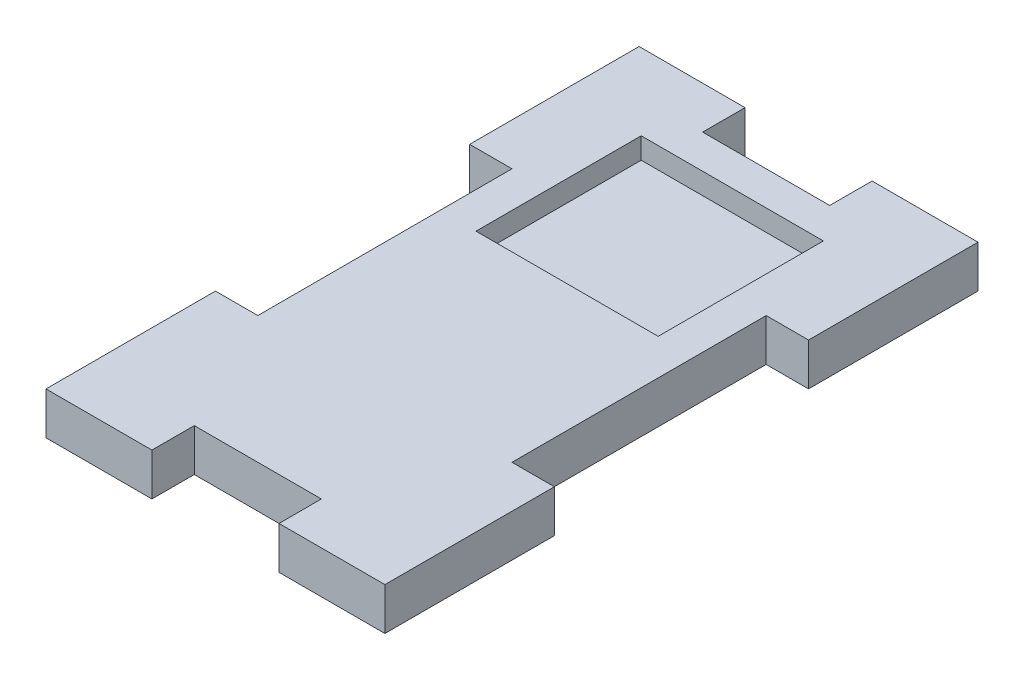
SolidWorks part; units mm, degrees
material "Acrylic (Medium-high impact)"
ref_plane "Front Plane" through (0, 0, 0) normal (0, 0, 1) x (1, 0, 0)
ref_plane "Top Plane" through (0, 0, 0) normal (0, 1, 0) x (1, 0, 0)
ref_plane "Right Plane" through (0, 0, 0) normal (1, 0, 0) x (0, 0, -1)
sketch "Sketch1" plane through (0, 0, 0) normal (0, 1, 0) x (1, 0, 0)
  line L1 (0, 0) -> (40, 0)
  line L2 (0, 0) -> (0, 70)
  line L3 (0, 70) -> (40, 70)
  line L4 (40, 0) -> (40, 70)
  dimension "D1" = 70
  dimension "D2" = 40
extrude "Boss-Extrude1" add sketch "Sketch1" along normal blind 5
sketch "Sketch3" plane through (0, 5, 0) normal (0, 1, 0) x (1, 0, 0)
  point P0 (15.5429, 20.9788)
  point P1 (15.5429, 20.9788)
sketch "Sketch4" plane through (0, 0, 0) normal (0, -1, 0) x (1, 0, 0)
  line L0 (20, 0) -> (20, -70) construction
  line L1 (30.75, -61) -> (9.25, -61)
  line L2 (30.75, -61) -> (30.75, -41.5)
  line L3 (30.75, -41.5) -> (9.25, -41.5)
  line L4 (9.25, -61) -> (9.25, -41.5)
  line L5 (30.75, -61) -> (9.25, -41.5) construction
  line L6 (30.75, -41.5) -> (9.25, -61) construction
  line L7 (40, -70) -> (0, -70) construction
  line L8 (0, 0) -> (40, 0) construction
  point P0 (20, -51.25)
  point P12 (0, 0)
  point P13 (0, 0)
  point P14 (0, 0)
  dimension "D1" = 19.5
  dimension "D2" = 21.5
  dimension "D4" = 9
extrude "Cut-Extrude2" cut sketch "Sketch4" along direction (0, -1, 0) on the side against the normal blind 2.5 from offset 2.5 offset against normal yes
sketch "Sketch5" plane through (0, 5, 0) normal (0, 1, 0) x (1, 0, 0)
  line L0 (0, 70) -> (0, 0) construction
  line L1 (0, 20) -> (5, 20)
  line L2 (0, 20) -> (0, 50)
  line L3 (0, 50) -> (5, 50)
  line L4 (5, 20) -> (5, 50)
  line L5 (40, 70) -> (0, 70) construction
  line L6 (27.5, 70) -> (12.5, 70)
  line L7 (27.5, 70) -> (27.5, 65)
  line L8 (27.5, 65) -> (12.5, 65)
  line L9 (12.5, 70) -> (12.5, 65)
  line L10 (40, 0) -> (40, 70) construction
  line L11 (40, 50) -> (35, 50)
  line L12 (40, 50) -> (40, 20)
  line L13 (40, 20) -> (35, 20)
  line L14 (35, 50) -> (35, 20)
  line L15 (0, 0) -> (40, 0) construction
  line L16 (12.5, 0) -> (27.5, 0)
  line L17 (12.5, 0) -> (12.5, 5)
  line L18 (12.5, 5) -> (27.5, 5)
  line L19 (27.5, 0) -> (27.5, 5)
  point P25 (0, 35)
  point P26 (20, 0)
  dimension "D1" = 5
  dimension "D2" = 30
  dimension "D3" = 15
extrude "Cut-Extrude3" cut sketch "Sketch5" against normal through all both and the other way through all
